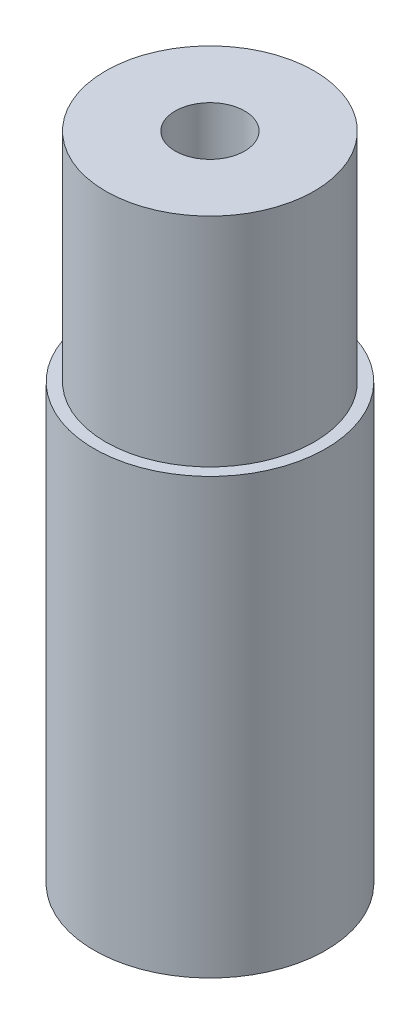
SolidWorks part; units mm, degrees
ref_plane "Front Plane" through (0, 0, 0) normal (0, 0, 1) x (1, 0, 0)
ref_plane "Top Plane" through (0, 0, 0) normal (0, 1, 0) x (1, 0, 0)
ref_plane "Right Plane" through (0, 0, 0) normal (1, 0, 0) x (0, 0, -1)
sketch "Sketch1" plane through (0, 0, 0) normal (0, 1, 0) x (1, 0, 0)
  circle A0 centre (0, 0) radius 5.08
extrude "Boss-Extrude1" add sketch "Sketch1" along normal blind 19.05
sketch "Sketch2" plane through (0, 19.05, 0) normal (0, 1, 0) x (1, 0, 0)
  circle A3 centre (0, 0) radius 4.572
  circle A4 centre (0, 0) radius 4.572
  dimension "D1" = 0.508
extrude "Boss-Extrude2" add sketch "Sketch2" along normal blind 9.525
sketch "Sketch3" plane through (0, 28.575, 0) normal (0, 1, 0) x (1, 0, 0)
  circle A0 centre (0, 0) radius 1.524
extrude "Cut-Extrude1" cut sketch "Sketch3" against normal blind 4.699
ref_axis "Axis1" through (0, 40.501, 0) along (0, -1, 0)
